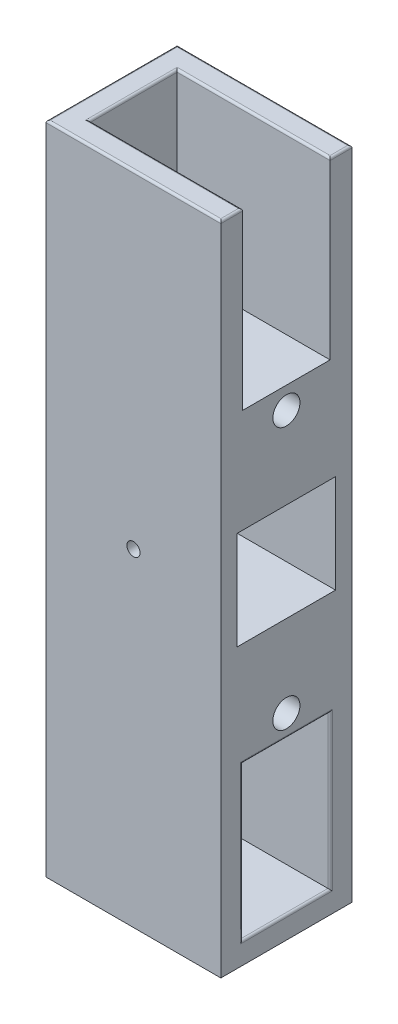
SolidWorks part; units mm, degrees
ref_plane "Front" through (0, 0, 0) normal (0, 0, 1) x (1, 0, 0)
ref_plane "Top" through (0, 0, 0) normal (0, 1, 0) x (1, 0, 0)
ref_plane "Right" through (0, 0, 0) normal (1, 0, 0) x (0, 0, -1)
sketch "Sketch1" plane through (0, 0, 0) normal (0, 1, 0) x (1, 0, 0)
  line L1 (-20, 15) -> (20, 15)
  line L2 (-20, 15) -> (-20, -15)
  line L3 (-20, -15) -> (20, -15)
  line L4 (20, 15) -> (20, -15)
  line L5 (-20, 15) -> (20, -15) construction
  line L6 (-20, -15) -> (20, 15) construction
  point P0 (0, 0)
  dimension "D1" = 30
  dimension "D2" = 40
extrude "Boss-Extrude1" add sketch "Sketch1" along normal blind 75 and the other way blind 75
sketch "Sketch3" plane through (20, 0, 0) normal (1, 0, 0) x (0, 0, -1)
  circle A0 centre (0, 30) radius 3.1
  dimension "D2" = 6.2
  dimension "D1" = 30
extrude "Cut-Extrude1" cut sketch "Sketch3" against normal blind 150
mirror "Mirror1" about plane through (0, 0, 0) normal (0, 1, 0) of "Cut-Extrude1"
sketch "Sketch4" plane through (0, 0, 0) normal (1, 0, 0) x (0, 0, -1)
  line L1 (-11.25, 11.25) -> (11.25, 11.25)
  line L2 (-11.25, 11.25) -> (-11.25, -11.25)
  line L3 (-11.25, -11.25) -> (11.25, -11.25)
  line L4 (11.25, 11.25) -> (11.25, -11.25)
  line L5 (-11.25, 11.25) -> (11.25, -11.25) construction
  line L6 (-11.25, -11.25) -> (11.25, 11.25) construction
  point P0 (0, 0)
  dimension "D1" = 22.5
  dimension "D2" = 22.5
extrude "Cut-Extrude2" cut sketch "Sketch4" against normal blind 150 and the other way blind 150
sketch "Sketch5" plane through (0, 0, -15) normal (0, 0, -1) x (-1, 0, 0)
  circle A0 centre (0, 0) radius 7.2
  dimension "D1" = 14.4
sketch "Sketch6" plane through (0, 0, 11.25) normal (0, 0, -1) x (-1, 0, 0)
  circle A0 centre (0, 0) radius 1.5
  dimension "D1" = 3
sketch "Sketch7" plane through (0, 75, 0) normal (0, 1, 0) x (1, 0, 0)
  line L0 (-20, -15) -> (20, -15) construction
  line L5 (-15, -10) -> (43.5907, -10)
  line L6 (-15, -10) -> (-15, 10)
  line L7 (-15, 10) -> (43.5907, 10)
  line L8 (43.5907, -10) -> (43.5907, 10)
  line L9 (-20, 15) -> (-20, -15) construction
  line L10 (20, 15) -> (-20, 15) construction
  point P0 (0, 0)
  dimension "D1" = 5
  dimension "D2" = 5
  dimension "D3" = 5
extrude "Cut-Extrude5" cut sketch "Sketch7" against normal blind 40
sketch "Sketch8" plane through (20, 0, 0) normal (1, 0, 0) x (0, 0, -1)
  line L0 (-15, -75) -> (15, -75) construction
  line L1 (-10, -70) -> (10, -70)
  line L2 (-10, -70) -> (-10, -35)
  line L3 (-10, -35) -> (10, -35)
  line L4 (10, -70) -> (10, -35)
  line L5 (-15, -75) -> (-15, 75) construction
  line L6 (15, -75) -> (15, 75) construction
  dimension "D1" = 5
  dimension "D2" = 5
  dimension "D3" = 5
  dimension "D4" = 40
extrude "Cut-Extrude6" cut sketch "Sketch8" against normal blind 35
fillet "Fillet2" radius 0.5 8 edges at (20, 75, -12.5) (2.5, 75, -10) (-15, 75, 0) (2.5, 75, 10) (20, 75, 12.5) (0, 75, -15) (-20, 75, 0) (0, 75, 15)
fillet "Fillet3" radius 0.5 4 edges at (20, -70, 0) (20, -52.5, 10) (20, -35, 0) (20, -52.5, -10)
extrude "Cut-Extrude7" cut sketch "Sketch6" against normal blind 10 and the other way blind 102 contours A0
